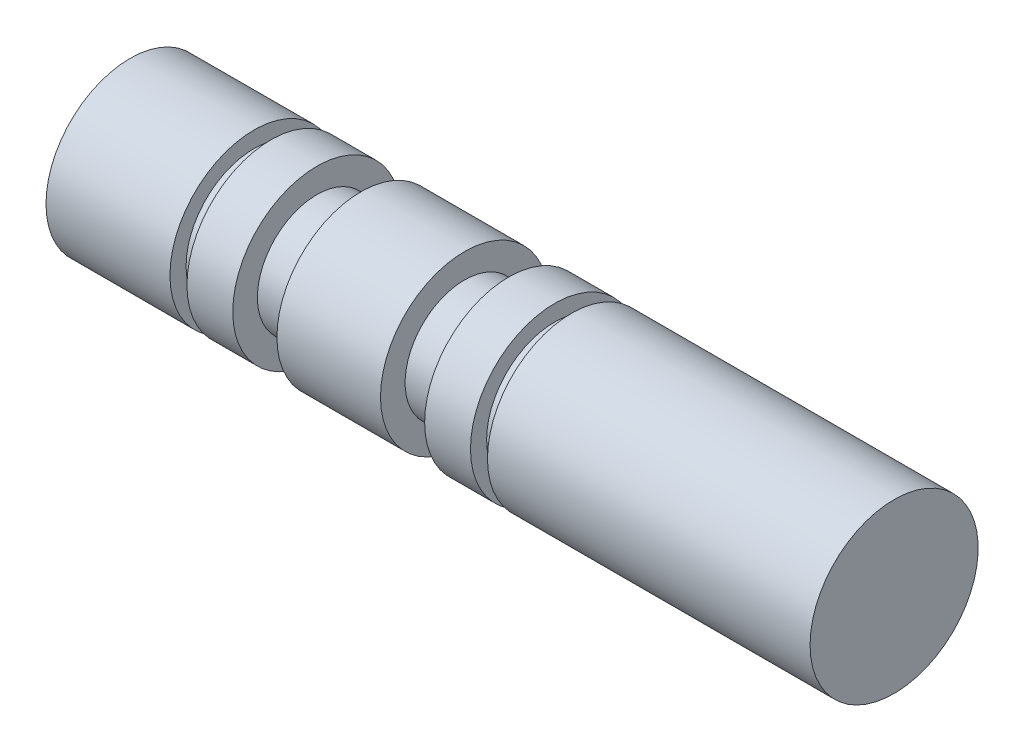
SolidWorks part; units mm, degrees
ref_plane "Спереди" through (0, 0, 0) normal (0, 0, 1) x (1, 0, 0)
ref_plane "Сверху" through (0, 0, 0) normal (0, 1, 0) x (1, 0, 0)
ref_plane "Справа" through (0, 0, 0) normal (1, 0, 0) x (0, 0, -1)
other "Configuration Table"
sketch "Эскиз1" plane through (0, 0, 0) normal (1, 0, 0) x (0, 0, -1)
  circle A0 centre (0, 0) radius 4.95
  circle A1 centre (0, 0) radius 3.5
  dimension "D1" = 9.9
  dimension "D2" = 7
extrude "Бобышка-Вытянуть1" add sketch "Эскиз1" along normal blind 45 contours A1 | A0 A1 region at (0, 0, 4.81) region at (0, 0, 0)
extrude "Вырез-Вытянуть1" cut sketch "Эскиз1<3>" along normal blind 2.6 from offset 11
sketch "Эскиз1<3>" plane through (0, 0, 0) normal (1, 0, 0) x (0, 0, -1) same geometry as "Эскиз1"
extrude "Вырез-Вытянуть2" cut sketch "Эскиз1<4>" along normal blind 2.6 from offset 19.7
sketch "Эскиз1<4>" plane through (0, 0, 0) normal (1, 0, 0) x (0, 0, -1) same geometry as "Эскиз1"
sketch "Эскиз2" plane through (0, 0, 0) normal (-1, 0, 0) x (0, 0, 1)
  circle A0 centre (0, 0) radius 2
  dimension "D1" = 4
extrude "Вырез-Вытянуть3" cut sketch "Эскиз2" against normal blind 10
sketch "Эскиз3" plane through (0, 0, 0) normal (0, 1, 0) x (1, 0, 0)
  line L0 (0, 4.95) -> (0, -4.95) construction
  circle A0 centre (4, 0) radius 1.25
  dimension "D1" = 2.5
  dimension "D2" = 4
extrude "Вырез-Вытянуть4" cut sketch "Эскиз3" against normal through all
sketch "Эскиз4" plane through (0, 0, 0) normal (-1, 0, 0) x (0, 0, 1)
  circle A0 centre (0, 0) radius 4
  circle A1 centre (0, 0) radius 4.95
  dimension "D1" = 8
extrude "Вырез-Вытянуть5" cut sketch "Эскиз4" along normal blind 1 from offset 8.3 offset against normal yes
extrude "Вырез-Вытянуть6" cut sketch "Эскиз4<2>" against normal blind 1 from offset 25 offset against normal yes
sketch "Эскиз4<2>" plane through (0, 0, 0) normal (-1, 0, 0) x (0, 0, 1) same geometry as "Эскиз4"
